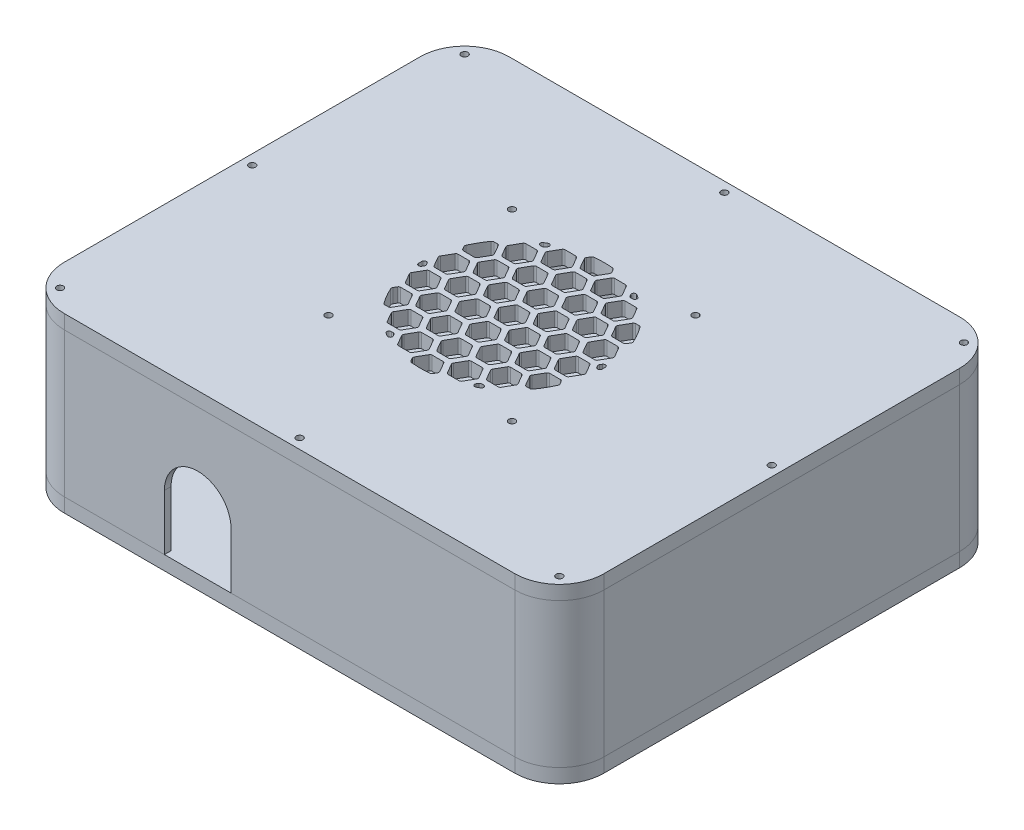
SolidWorks part; units mm, degrees
ref_plane "Front Plane" through (0, 0, 0) normal (0, 0, 1) x (1, 0, 0)
ref_plane "Top Plane" through (0, 0, 0) normal (0, 1, 0) x (1, 0, 0)
ref_plane "Right Plane" through (0, 0, 0) normal (1, 0, 0) x (0, 0, -1)
sketch "Sketch1" plane through (0, 0, 0) normal (0, 1, 0) x (1, 0, 0)
  line L0 (0, 100) -> (242.6, 100) construction
  line L1 (0, 0) -> (242.6, 0)
  line L2 (0, 0) -> (0, 200)
  line L3 (0, 200) -> (242.6, 200)
  line L4 (242.6, 0) -> (242.6, 200)
  line L6 (89, 170) -> (165.6, 170) construction
  line L7 (89, 170) -> (89, 15) construction
  line L8 (89, 15) -> (165.6, 15) construction
  line L9 (165.6, 170) -> (165.6, 15) construction
  line L10 (15, 106) -> (84, 106) construction
  line L11 (15, 106) -> (15, 15) construction
  line L12 (15, 15) -> (84, 15) construction
  line L13 (84, 106) -> (84, 15) construction
  line L14 (170.6, 127) -> (230.6, 127) construction
  line L15 (170.6, 127) -> (170.6, 15) construction
  line L16 (170.6, 15) -> (230.6, 15) construction
  line L17 (230.6, 127) -> (230.6, 15) construction
  line L22 (15, 170) -> (84, 170) construction
  line L23 (15, 170) -> (15, 121) construction
  line L24 (15, 121) -> (84, 121) construction
  line L25 (84, 170) -> (84, 121) construction
  dimension "D1" = 76.6
  dimension "D2" = 155
  dimension "D3" = 69
  dimension "D4" = 91
  dimension "D5" = 60
  dimension "D6" = 112
  dimension "D7" = 15
  dimension "D8" = 5
  dimension "D9" = 5
  dimension "D10" = 12
  dimension "D11" = 30
  dimension "D12" = 15
  dimension "D13" = 15
extrude "Boss-Extrude1" add sketch "Sketch1" along normal blind 6.35
fillet "Fillet1" radius 20 4 edges at (0, 3.175, -200) (242.6, 3.175, -200) (242.6, 3.175, 0) (0, 3.175, 0)
sketch "Sketch2" plane through (0, 6.35, 0) normal (0, 1, 0) x (1, 0, 0)
  line L0 (89, 170) -> (165.6, 170) construction
  line L1 (92.6, 167) -> (162, 167) construction
  line L2 (92.6, 167) -> (92.6, 25) construction
  line L3 (92.6, 25) -> (162, 25) construction
  line L4 (162, 167) -> (162, 25) construction
  line L5 (170.6, 127) -> (230.6, 127) construction
  line L6 (175.6, 65) -> (225.6, 65) construction
  line L7 (175.6, 65) -> (175.6, 40) construction
  line L8 (175.6, 40) -> (225.6, 40) construction
  line L9 (225.6, 65) -> (225.6, 40) construction
  line L11 (15, 170) -> (15, 121) construction
  line L12 (80.996, 125.18) -> (18.004, 125.18) construction
  line L13 (80.996, 125.18) -> (80.996, 165.82) construction
  line L14 (80.996, 165.82) -> (18.004, 165.82) construction
  line L15 (18.004, 125.18) -> (18.004, 165.82) construction
  line L16 (80.996, 125.18) -> (18.004, 165.82) construction
  line L17 (80.996, 165.82) -> (18.004, 125.18) construction
  line L18 (15, 170) -> (84, 170) construction
  line L19 (20, 0) -> (222.6, 0) construction
  circle A0 centre (92.6, 167) radius 1.5
  circle A1 centre (92.6, 25) radius 1.5
  circle A2 centre (162, 25) radius 1.5
  circle A3 centre (162, 167) radius 1.5
  circle A4 centre (175.6, 65) radius 1.5
  circle A5 centre (175.6, 40) radius 1.5
  circle A6 centre (225.6, 65) radius 1.5
  circle A7 centre (225.6, 40) radius 1.5
  circle A8 centre (18.004, 165.82) radius 1.5
  circle A9 centre (80.996, 165.82) radius 1.5
  circle A10 centre (80.996, 125.18) radius 1.5
  circle A11 centre (18.004, 125.18) radius 1.5
  point P6 (127.3, 167)
  point P7 (127.3, 170)
  point P20 (200.6, 65)
  point P23 (200.6, 127)
  point P26 (49.5, 145.5)
  point P34 (15, 145.5)
  point P37 (49.5, 170)
  dimension "D6" = 3
  dimension "D1" = 69.4
  dimension "D2" = 142
  dimension "D3" = 3
  dimension "D4" = 50
  dimension "D5" = 25
  dimension "D7" = 40
  dimension "D8" = 62.992
  dimension "D9" = 40.64
extrude "Cut-Extrude1" cut sketch "Sketch2" against normal through all
sketch "Sketch3" plane through (0, 6.35, 0) normal (0, 1, 0) x (1, 0, 0)
  line L21 (20, 20) -> (9.0398, 9.0398) construction
  line L22 (0, 180) -> (0, 20) construction
  line L23 (6.9185, 11.1612) -> (6.0465, 10.2892)
  line L24 (11.1612, 6.9185) -> (10.2892, 6.0465)
  line L25 (0, 100) -> (242.6, 100) construction
  line L26 (121.3, 200) -> (121.3, 0) construction
  line L27 (231.4388, 6.9185) -> (232.3108, 6.0465)
  line L28 (235.6815, 11.1612) -> (236.5535, 10.2892)
  line L29 (235.6815, 188.8388) -> (236.5535, 189.7108)
  line L30 (231.4388, 193.0815) -> (232.3108, 193.9535)
  line L31 (11.1612, 193.0815) -> (10.2892, 193.9535)
  line L32 (6.9185, 188.8388) -> (6.0465, 189.7108)
  line L33 (242.6, 20) -> (242.6, 180) construction
  line L34 (20, 0) -> (222.6, 0) construction
  line L35 (222.6, 200) -> (20, 200) construction
  line L36 (20, 20) -> (20, 12.5101) construction
  line L37 (3, 180) -> (3, 20)
  line L38 (20, 3) -> (222.6, 3)
  line L39 (239.6, 20) -> (239.6, 180)
  line L40 (222.6, 197) -> (20, 197)
  line L41 (222.6, 200) -> (20, 200)
  line L42 (0, 180) -> (0, 20)
  line L43 (20, 0) -> (222.6, 0)
  line L44 (242.6, 20) -> (242.6, 180)
  line L45 (222.6, 200) -> (20, 200)
  line L46 (0, 180) -> (0, 20)
  line L47 (20, 0) -> (222.6, 0)
  line L48 (242.6, 20) -> (242.6, 180)
  line L49 (4.5, 103) -> (3, 103)
  line L50 (3, 103) -> (3, 97)
  line L51 (3, 97) -> (4.5, 97)
  line L52 (239.6, 103) -> (239.6, 97)
  line L53 (238.1, 103) -> (239.6, 103)
  line L54 (239.6, 97) -> (238.1, 97)
  line L55 (118.3, 195.5) -> (118.3, 197)
  line L56 (124.3, 195.5) -> (124.3, 197)
  line L57 (118.3, 197) -> (124.3, 197)
  line L58 (118.3, 4.5) -> (118.3, 3)
  line L59 (124.3, 4.5) -> (124.3, 3)
  line L60 (118.3, 3) -> (124.3, 3)
  arc A22 (10.2892, 193.9535) -> (6.0465, 189.7108) centre (20, 180) ccw
  arc A24 (6.0465, 10.2892) -> (10.2892, 6.0465) centre (20, 20) ccw
  arc A26 (232.3108, 6.0465) -> (236.5535, 10.2892) centre (222.6, 20) ccw
  arc A28 (236.5535, 189.7108) -> (232.3108, 193.9535) centre (222.6, 180) ccw
  arc A43 (11.1612, 6.9185) -> (6.9185, 11.1612) centre (9.0398, 9.0398) ccw
  circle A44 centre (9.0398, 9.0398) radius 1.5
  circle A45 centre (233.5602, 9.0398) radius 1.5
  arc A46 (231.4388, 6.9185) -> (235.6815, 11.1612) centre (233.5602, 9.0398) cw
  circle A47 centre (233.5602, 190.9602) radius 1.5
  arc A48 (231.4388, 193.0815) -> (235.6815, 188.8388) centre (233.5602, 190.9602) ccw
  circle A49 centre (9.0398, 190.9602) radius 1.5
  arc A50 (11.1612, 193.0815) -> (6.9185, 188.8388) centre (9.0398, 190.9602) cw
  arc A51 (222.6, 0) -> (242.6, 20) centre (222.6, 20) ccw construction
  arc A52 (0, 20) -> (20, 0) centre (20, 20) ccw construction
  arc A53 (242.6, 180) -> (222.6, 200) centre (222.6, 180) ccw construction
  arc A54 (20, 200) -> (0, 180) centre (20, 180) ccw construction
  arc A55 (3, 20) -> (20, 3) centre (20, 20) ccw
  arc A56 (222.6, 3) -> (239.6, 20) centre (222.6, 20) ccw
  arc A57 (239.6, 180) -> (222.6, 197) centre (222.6, 180) ccw
  arc A58 (20, 197) -> (3, 180) centre (20, 180) ccw
  arc A59 (20, 200) -> (0, 180) centre (20, 180) ccw
  arc A60 (0, 20) -> (20, 0) centre (20, 20) ccw
  arc A61 (222.6, 0) -> (242.6, 20) centre (222.6, 20) ccw
  arc A62 (242.6, 180) -> (222.6, 200) centre (222.6, 180) ccw
  arc A63 (20, 200) -> (0, 180) centre (20, 180) ccw
  arc A64 (0, 20) -> (20, 0) centre (20, 20) ccw
  arc A65 (222.6, 0) -> (242.6, 20) centre (222.6, 20) ccw
  arc A66 (242.6, 180) -> (222.6, 200) centre (222.6, 180) ccw
  arc A67 (4.5, 97) -> (4.5, 103) centre (4.5, 100) ccw
  circle A68 centre (4.5, 100) radius 1.5
  arc A69 (238.1, 97) -> (238.1, 103) centre (238.1, 100) cw
  circle A70 centre (238.1, 100) radius 1.5
  circle A71 centre (121.3, 195.5) radius 1.5
  arc A72 (118.3, 195.5) -> (124.3, 195.5) centre (121.3, 195.5) ccw
  circle A73 centre (121.3, 4.5) radius 1.5
  arc A74 (118.3, 4.5) -> (124.3, 4.5) centre (121.3, 4.5) cw
  line M50 (222.6, 200) -> (20, 200)
  arc M51 (20, 200) -> (0, 180) centre (20, 180) ccw
  line M52 (0, 180) -> (0, 20)
  arc M53 (0, 20) -> (20, 0) centre (20, 20) ccw
  line M54 (20, 0) -> (222.6, 0)
  arc M55 (222.6, 0) -> (242.6, 20) centre (222.6, 20) ccw
  line M56 (242.6, 20) -> (242.6, 180)
  arc M57 (242.6, 180) -> (222.6, 200) centre (222.6, 180) ccw
  dimension "D3" = 0
  dimension "D4" = 6
  dimension "D5" = 3
  dimension "D1" = 3
  dimension "D7" = 3
  dimension "D6" = 3
  dimension "D2" = 45
extrude "Boss-Extrude2" add sketch "Sketch3" along normal blind 65 separate body contours M57 M50 M51 M52 M53 M54 M55 M56 | A50 L31 A22 A49 L32 | L37 A68 L50 L51 A67 L49 | A24 A44 L24 A43 L23 | A46 L27 A26 A45 L28 | A74 L58 L38 A73 L60 L59 | L39 A70 L52 L53 A69 L54 | L30 A48 L29 A28 A47 | L55 A72 L56 L40 A71 L57 region at (11.1012, 6.35, -11.1012) region at (3.075, 6.35, -98.5) region at (118.375, 6.35, -3.75) region at (7.0266, 6.35, -190.8543) region at (231.9348, 6.35, -6.5425) region at (119.8, 6.35, -196.925) region at (238.85, 6.35, -97.075) region at (233.4543, 6.35, -192.9734) region at (236.5198, 6.35, -193.9198)
fillet "Fillet5" radius 2 16 edges at (10.2892, 38.85, -193.9535) (6.0465, 38.85, -189.7108) (3, 38.85, -103) (3, 38.85, -97) (6.0465, 38.85, -10.2892) (10.2892, 38.85, -6.0465) (118.3, 38.85, -3) (124.3, 38.85, -3) (232.3108, 38.85, -6.0465) (236.5535, 38.85, -10.2892) (239.6, 38.85, -97) (239.6, 38.85, -103) (232.3108, 38.85, -193.9535) (124.3, 38.85, -197) (118.3, 38.85, -197) (236.5535, 38.85, -189.7108)
sketch "Sketch4" plane through (0, 71.35, 0) normal (0, 1, 0) x (1, 0, 0)
  line L4 (0, 180) -> (0, 20)
  line L5 (222.6, 200) -> (20, 200)
  line L6 (242.6, 20) -> (242.6, 180)
  line L7 (20, 0) -> (222.6, 0)
  line L8 (0, 180) -> (0, 20)
  line L9 (222.6, 200) -> (20, 200)
  line L10 (242.6, 20) -> (242.6, 180)
  line L11 (20, 0) -> (222.6, 0)
  arc A4 (20, 200) -> (0, 180) centre (20, 180) ccw
  arc A5 (242.6, 180) -> (222.6, 200) centre (222.6, 180) ccw
  arc A6 (222.6, 0) -> (242.6, 20) centre (222.6, 20) ccw
  arc A7 (0, 20) -> (20, 0) centre (20, 20) ccw
  arc A8 (20, 200) -> (0, 180) centre (20, 180) ccw
  arc A9 (242.6, 180) -> (222.6, 200) centre (222.6, 180) ccw
  arc A10 (222.6, 0) -> (242.6, 20) centre (222.6, 20) ccw
  arc A11 (0, 20) -> (20, 0) centre (20, 20) ccw
  dimension "D1" = 0
extrude "Boss-Extrude4" add sketch "Sketch4" along normal blind 6.35 separate body
sketch "Sketch5" plane through (0, 77.7, 0) normal (0, 1, 0) x (1, 0, 0)
  line L1 (80.05, 141.25) -> (162.55, 141.25) construction
  line L2 (80.05, 141.25) -> (80.05, 58.75) construction
  line L3 (80.05, 58.75) -> (162.55, 58.75) construction
  line L4 (162.55, 141.25) -> (162.55, 58.75) construction
  line L5 (80.05, 141.25) -> (162.55, 58.75) construction
  line L6 (80.05, 58.75) -> (162.55, 141.25) construction
  line L8 (222.6, 200) -> (20, 200) construction
  line L9 (0, 180) -> (0, 20) construction
  circle A0 centre (80.05, 141.25) radius 1.5
  circle A1 centre (80.05, 58.75) radius 1.5
  circle A2 centre (162.55, 58.75) radius 1.5
  circle A3 centre (162.55, 141.25) radius 1.5
  point P0 (121.3, 100)
  point P11 (121.3, 200)
  point P12 (0, 100)
  dimension "D2" = 3
  dimension "D1" = 82.5
extrude "Cut-Extrude2" cut sketch "Sketch5" against normal through all
sketch "Sketch6" plane through (0, 77.7, 0) normal (0, 1, 0) x (1, 0, 0)
  circle A20 centre (121.3, 4.5) radius 1.5 construction
  circle A21 centre (233.5602, 9.0398) radius 1.5 construction
  circle A22 centre (238.1, 100) radius 1.5 construction
  circle A23 centre (233.5602, 190.9602) radius 1.5 construction
  circle A24 centre (121.3, 195.5) radius 1.5 construction
  circle A25 centre (9.0398, 190.9602) radius 1.5 construction
  circle A26 centre (4.5, 100) radius 1.5 construction
  circle A27 centre (9.0398, 9.0398) radius 1.5 construction
  circle A28 centre (121.3, 4.5) radius 1.5
  circle A29 centre (233.5602, 9.0398) radius 1.5
  circle A30 centre (238.1, 100) radius 1.5
  circle A31 centre (233.5602, 190.9602) radius 1.5
  circle A32 centre (121.3, 195.5) radius 1.5
  circle A33 centre (9.0398, 190.9602) radius 1.5
  circle A34 centre (4.5, 100) radius 1.5
  circle A35 centre (9.0398, 9.0398) radius 1.5
extrude "Cut-Extrude3" cut sketch "Sketch6" against normal through all
sketch "Sketch7" plane through (0, 77.7, 0) normal (0, 1, 0) x (1, 0, 0)
  line L0 (80.05, 141.25) -> (162.55, 141.25) construction
  line L1 (80.05, 141.25) -> (80.05, 58.75) construction
  line L2 (80.05, 58.75) -> (162.55, 58.75) construction
  line L3 (162.55, 141.25) -> (162.55, 58.75) construction
  line L4 (80.05, 141.25) -> (162.55, 141.25) construction
  line L5 (80.05, 141.25) -> (80.05, 58.75) construction
  line L6 (80.05, 58.75) -> (162.55, 58.75) construction
  line L7 (162.55, 141.25) -> (162.55, 58.75) construction
  line L8 (157.7952, 124.5346) -> (151.7952, 124.5346)
  line L9 (124.3, 105.1962) -> (118.3, 105.1962)
  line L10 (118.3, 105.1962) -> (115.3, 100)
  line L11 (115.3, 100) -> (118.3, 94.8038)
  line L12 (118.3, 94.8038) -> (124.3, 94.8038)
  line L13 (124.3, 94.8038) -> (127.3, 100)
  line L14 (127.3, 100) -> (124.3, 105.1962)
  line L15 (138.4651, 106.4462) -> (135.4651, 111.6423)
  line L16 (135.4651, 111.6423) -> (129.4651, 111.6423)
  line L17 (129.4651, 111.6423) -> (126.4651, 106.4462)
  line L18 (126.4651, 106.4462) -> (129.4651, 101.25)
  line L19 (129.4651, 101.25) -> (135.4651, 101.25)
  line L20 (135.4651, 101.25) -> (138.4651, 106.4462)
  line L21 (127.3, 112.8923) -> (124.3, 118.0885)
  line L22 (124.3, 118.0885) -> (118.3, 118.0885)
  line L23 (118.3, 118.0885) -> (115.3, 112.8923)
  line L24 (115.3, 112.8923) -> (118.3, 107.6962)
  line L25 (118.3, 107.6962) -> (124.3, 107.6962)
  line L26 (124.3, 107.6962) -> (127.3, 112.8923)
  line L27 (135.4651, 124.5346) -> (129.4651, 124.5346)
  line L28 (129.4651, 124.5346) -> (126.4651, 119.3385)
  line L29 (126.4651, 119.3385) -> (129.4651, 114.1423)
  line L30 (129.4651, 114.1423) -> (135.4651, 114.1423)
  line L31 (135.4651, 114.1423) -> (138.4651, 119.3385)
  line L32 (138.4651, 119.3385) -> (135.4651, 124.5346)
  line L33 (151.7952, 124.5346) -> (148.7952, 119.3385)
  line L34 (148.7952, 119.3385) -> (151.7952, 114.1423)
  line L35 (151.7952, 114.1423) -> (157.7952, 114.1423)
  line L36 (157.7952, 114.1423) -> (160.7952, 119.3385)
  line L37 (160.7952, 119.3385) -> (157.7952, 124.5346)
  line L38 (149.6301, 112.8923) -> (146.6301, 118.0885)
  line L39 (146.6301, 118.0885) -> (140.6301, 118.0885)
  line L40 (140.6301, 118.0885) -> (137.6301, 112.8923)
  line L41 (137.6301, 112.8923) -> (140.6301, 107.6962)
  line L42 (140.6301, 107.6962) -> (146.6301, 107.6962)
  line L43 (146.6301, 107.6962) -> (149.6301, 112.8923)
  line L44 (146.6301, 105.1962) -> (140.6301, 105.1962)
  line L45 (140.6301, 105.1962) -> (137.6301, 100)
  line L46 (137.6301, 100) -> (140.6301, 94.8038)
  line L47 (140.6301, 94.8038) -> (146.6301, 94.8038)
  line L48 (146.6301, 94.8038) -> (149.6301, 100)
  line L49 (149.6301, 100) -> (146.6301, 105.1962)
  line L50 (160.7952, 106.4462) -> (157.7952, 111.6423)
  line L51 (157.7952, 111.6423) -> (151.7952, 111.6423)
  line L52 (151.7952, 111.6423) -> (148.7952, 106.4462)
  line L53 (148.7952, 106.4462) -> (151.7952, 101.25)
  line L54 (151.7952, 101.25) -> (157.7952, 101.25)
  line L55 (157.7952, 101.25) -> (160.7952, 106.4462)
  line L56 (180.1253, 124.5346) -> (174.1253, 124.5346)
  line L57 (174.1253, 124.5346) -> (171.1253, 119.3385)
  line L58 (171.1253, 119.3385) -> (174.1253, 114.1423)
  line L59 (174.1253, 114.1423) -> (180.1253, 114.1423)
  line L60 (180.1253, 114.1423) -> (183.1253, 119.3385)
  line L61 (183.1253, 119.3385) -> (180.1253, 124.5346)
  line L62 (171.9603, 112.8923) -> (168.9603, 118.0885)
  line L63 (168.9603, 118.0885) -> (162.9603, 118.0885)
  line L64 (162.9603, 118.0885) -> (159.9603, 112.8923)
  line L65 (159.9603, 112.8923) -> (162.9603, 107.6962)
  line L66 (162.9603, 107.6962) -> (168.9603, 107.6962)
  line L67 (168.9603, 107.6962) -> (171.9603, 112.8923)
  line L68 (168.9603, 105.1962) -> (162.9603, 105.1962)
  line L69 (162.9603, 105.1962) -> (159.9603, 100)
  line L70 (159.9603, 100) -> (162.9603, 94.8038)
  line L71 (162.9603, 94.8038) -> (168.9603, 94.8038)
  line L72 (168.9603, 94.8038) -> (171.9603, 100)
  line L73 (171.9603, 100) -> (168.9603, 105.1962)
  line L74 (183.1253, 106.4462) -> (180.1253, 111.6423)
  line L75 (180.1253, 111.6423) -> (174.1253, 111.6423)
  line L76 (174.1253, 111.6423) -> (171.1253, 106.4462)
  line L77 (171.1253, 106.4462) -> (174.1253, 101.25)
  line L78 (174.1253, 101.25) -> (180.1253, 101.25)
  line L79 (180.1253, 101.25) -> (183.1253, 106.4462)
  line L80 (157.7952, 150.3192) -> (151.7952, 150.3192)
  line L81 (151.7952, 150.3192) -> (148.7952, 145.1231)
  line L82 (148.7952, 145.1231) -> (151.7952, 139.9269)
  line L83 (151.7952, 139.9269) -> (157.7952, 139.9269)
  line L84 (157.7952, 139.9269) -> (160.7952, 145.1231)
  line L85 (160.7952, 145.1231) -> (157.7952, 150.3192)
  line L86 (149.6301, 138.6769) -> (146.6301, 143.8731)
  line L87 (146.6301, 143.8731) -> (140.6301, 143.8731)
  line L88 (140.6301, 143.8731) -> (137.6301, 138.6769)
  line L89 (137.6301, 138.6769) -> (140.6301, 133.4808)
  line L90 (140.6301, 133.4808) -> (146.6301, 133.4808)
  line L91 (146.6301, 133.4808) -> (149.6301, 138.6769)
  line L92 (146.6301, 130.9808) -> (140.6301, 130.9808)
  line L93 (140.6301, 130.9808) -> (137.6301, 125.7846)
  line L94 (137.6301, 125.7846) -> (140.6301, 120.5885)
  line L95 (140.6301, 120.5885) -> (146.6301, 120.5885)
  line L96 (146.6301, 120.5885) -> (149.6301, 125.7846)
  line L97 (149.6301, 125.7846) -> (146.6301, 130.9808)
  line L98 (160.7952, 132.2308) -> (157.7952, 137.4269)
  line L99 (157.7952, 137.4269) -> (151.7952, 137.4269)
  line L100 (151.7952, 137.4269) -> (148.7952, 132.2308)
  line L101 (148.7952, 132.2308) -> (151.7952, 127.0346)
  line L102 (151.7952, 127.0346) -> (157.7952, 127.0346)
  line L103 (157.7952, 127.0346) -> (160.7952, 132.2308)
  line L104 (180.1253, 150.3192) -> (174.1253, 150.3192)
  line L105 (174.1253, 150.3192) -> (171.1253, 145.1231)
  line L106 (171.1253, 145.1231) -> (174.1253, 139.9269)
  line L107 (174.1253, 139.9269) -> (180.1253, 139.9269)
  line L108 (180.1253, 139.9269) -> (183.1253, 145.1231)
  line L109 (183.1253, 145.1231) -> (180.1253, 150.3192)
  line L110 (171.9603, 138.6769) -> (168.9603, 143.8731)
  line L111 (168.9603, 143.8731) -> (162.9603, 143.8731)
  line L112 (162.9603, 143.8731) -> (159.9603, 138.6769)
  line L113 (159.9603, 138.6769) -> (162.9603, 133.4808)
  line L114 (162.9603, 133.4808) -> (168.9603, 133.4808)
  line L115 (168.9603, 133.4808) -> (171.9603, 138.6769)
  line L116 (168.9603, 130.9808) -> (162.9603, 130.9808)
  line L117 (162.9603, 130.9808) -> (159.9603, 125.7846)
  line L118 (159.9603, 125.7846) -> (162.9603, 120.5885)
  line L119 (162.9603, 120.5885) -> (168.9603, 120.5885)
  line L120 (168.9603, 120.5885) -> (171.9603, 125.7846)
  line L121 (171.9603, 125.7846) -> (168.9603, 130.9808)
  line L122 (183.1253, 132.2308) -> (180.1253, 137.4269)
  line L123 (180.1253, 137.4269) -> (174.1253, 137.4269)
  line L124 (174.1253, 137.4269) -> (171.1253, 132.2308)
  line L125 (171.1253, 132.2308) -> (174.1253, 127.0346)
  line L126 (174.1253, 127.0346) -> (180.1253, 127.0346)
  line L127 (180.1253, 127.0346) -> (183.1253, 132.2308)
  line L128 (135.4651, 150.3192) -> (129.4651, 150.3192)
  line L129 (129.4651, 150.3192) -> (126.4651, 145.1231)
  line L130 (126.4651, 145.1231) -> (129.4651, 139.9269)
  line L131 (129.4651, 139.9269) -> (135.4651, 139.9269)
  line L132 (135.4651, 139.9269) -> (138.4651, 145.1231)
  line L133 (138.4651, 145.1231) -> (135.4651, 150.3192)
  line L134 (127.3, 138.6769) -> (124.3, 143.8731)
  line L135 (124.3, 143.8731) -> (118.3, 143.8731)
  line L136 (118.3, 143.8731) -> (115.3, 138.6769)
  line L137 (115.3, 138.6769) -> (118.3, 133.4808)
  line L138 (118.3, 133.4808) -> (124.3, 133.4808)
  line L139 (124.3, 133.4808) -> (127.3, 138.6769)
  line L140 (124.3, 130.9808) -> (118.3, 130.9808)
  line L141 (118.3, 130.9808) -> (115.3, 125.7846)
  line L142 (115.3, 125.7846) -> (118.3, 120.5885)
  line L143 (118.3, 120.5885) -> (124.3, 120.5885)
  line L144 (124.3, 120.5885) -> (127.3, 125.7846)
  line L145 (127.3, 125.7846) -> (124.3, 130.9808)
  line L146 (138.4651, 132.2308) -> (135.4651, 137.4269)
  line L147 (135.4651, 137.4269) -> (129.4651, 137.4269)
  line L148 (129.4651, 137.4269) -> (126.4651, 132.2308)
  line L149 (126.4651, 132.2308) -> (129.4651, 127.0346)
  line L150 (129.4651, 127.0346) -> (135.4651, 127.0346)
  line L151 (135.4651, 127.0346) -> (138.4651, 132.2308)
  line L152 (124.3, 92.3038) -> (118.3, 92.3038)
  line L153 (118.3, 92.3038) -> (115.3, 87.1077)
  line L154 (115.3, 87.1077) -> (118.3, 81.9115)
  line L155 (118.3, 81.9115) -> (124.3, 81.9115)
  line L156 (124.3, 81.9115) -> (127.3, 87.1077)
  line L157 (127.3, 87.1077) -> (124.3, 92.3038)
  line L158 (138.4651, 93.5538) -> (135.4651, 98.75)
  line L159 (135.4651, 98.75) -> (129.4651, 98.75)
  line L160 (129.4651, 98.75) -> (126.4651, 93.5538)
  line L161 (126.4651, 93.5538) -> (129.4651, 88.3577)
  line L162 (129.4651, 88.3577) -> (135.4651, 88.3577)
  line L163 (135.4651, 88.3577) -> (138.4651, 93.5538)
  line L164 (160.7952, 93.5538) -> (157.7952, 98.75)
  line L165 (157.7952, 98.75) -> (151.7952, 98.75)
  line L166 (151.7952, 98.75) -> (148.7952, 93.5538)
  line L167 (148.7952, 93.5538) -> (151.7952, 88.3577)
  line L168 (151.7952, 88.3577) -> (157.7952, 88.3577)
  line L169 (157.7952, 88.3577) -> (160.7952, 93.5538)
  line L170 (168.9603, 92.3038) -> (162.9603, 92.3038)
  line L171 (162.9603, 92.3038) -> (159.9603, 87.1077)
  line L172 (159.9603, 87.1077) -> (162.9603, 81.9115)
  line L173 (162.9603, 81.9115) -> (168.9603, 81.9115)
  line L174 (168.9603, 81.9115) -> (171.9603, 87.1077)
  line L175 (171.9603, 87.1077) -> (168.9603, 92.3038)
  line L176 (146.6301, 92.3038) -> (140.6301, 92.3038)
  line L177 (140.6301, 92.3038) -> (137.6301, 87.1077)
  line L178 (137.6301, 87.1077) -> (140.6301, 81.9115)
  line L179 (140.6301, 81.9115) -> (146.6301, 81.9115)
  line L180 (146.6301, 81.9115) -> (149.6301, 87.1077)
  line L181 (149.6301, 87.1077) -> (146.6301, 92.3038)
  line L182 (124.3, 79.4115) -> (118.3, 79.4115)
  line L183 (118.3, 79.4115) -> (115.3, 74.2154)
  line L184 (115.3, 74.2154) -> (118.3, 69.0192)
  line L185 (118.3, 69.0192) -> (124.3, 69.0192)
  line L186 (124.3, 69.0192) -> (127.3, 74.2154)
  line L187 (127.3, 74.2154) -> (124.3, 79.4115)
  line L188 (138.4651, 80.6615) -> (135.4651, 85.8577)
  line L189 (135.4651, 85.8577) -> (129.4651, 85.8577)
  line L190 (129.4651, 85.8577) -> (126.4651, 80.6615)
  line L191 (126.4651, 80.6615) -> (129.4651, 75.4654)
  line L192 (129.4651, 75.4654) -> (135.4651, 75.4654)
  line L193 (135.4651, 75.4654) -> (138.4651, 80.6615)
  line L194 (160.7952, 80.6615) -> (157.7952, 85.8577)
  line L195 (157.7952, 85.8577) -> (151.7952, 85.8577)
  line L196 (151.7952, 85.8577) -> (148.7952, 80.6615)
  line L197 (148.7952, 80.6615) -> (151.7952, 75.4654)
  line L198 (151.7952, 75.4654) -> (157.7952, 75.4654)
  line L199 (157.7952, 75.4654) -> (160.7952, 80.6615)
  line L200 (168.9603, 79.4115) -> (162.9603, 79.4115)
  line L201 (162.9603, 79.4115) -> (159.9603, 74.2154)
  line L202 (159.9603, 74.2154) -> (162.9603, 69.0192)
  line L203 (162.9603, 69.0192) -> (168.9603, 69.0192)
  line L204 (168.9603, 69.0192) -> (171.9603, 74.2154)
  line L205 (171.9603, 74.2154) -> (168.9603, 79.4115)
  line L206 (146.6301, 79.4115) -> (140.6301, 79.4115)
  line L207 (140.6301, 79.4115) -> (137.6301, 74.2154)
  line L208 (137.6301, 74.2154) -> (140.6301, 69.0192)
  line L209 (140.6301, 69.0192) -> (146.6301, 69.0192)
  line L210 (146.6301, 69.0192) -> (149.6301, 74.2154)
  line L211 (149.6301, 74.2154) -> (146.6301, 79.4115)
  line L212 (124.3, 66.5192) -> (118.3, 66.5192)
  line L213 (118.3, 66.5192) -> (115.3, 61.3231)
  line L214 (115.3, 61.3231) -> (118.3, 56.1269)
  line L215 (118.3, 56.1269) -> (124.3, 56.1269)
  line L216 (124.3, 56.1269) -> (127.3, 61.3231)
  line L217 (127.3, 61.3231) -> (124.3, 66.5192)
  line L218 (138.4651, 67.7692) -> (135.4651, 72.9654)
  line L219 (135.4651, 72.9654) -> (129.4651, 72.9654)
  line L220 (129.4651, 72.9654) -> (126.4651, 67.7692)
  line L221 (126.4651, 67.7692) -> (129.4651, 62.5731)
  line L222 (129.4651, 62.5731) -> (135.4651, 62.5731)
  line L223 (135.4651, 62.5731) -> (138.4651, 67.7692)
  line L224 (160.7952, 67.7692) -> (157.7952, 72.9654)
  line L225 (157.7952, 72.9654) -> (151.7952, 72.9654)
  line L226 (151.7952, 72.9654) -> (148.7952, 67.7692)
  line L227 (148.7952, 67.7692) -> (151.7952, 62.5731)
  line L228 (151.7952, 62.5731) -> (157.7952, 62.5731)
  line L229 (157.7952, 62.5731) -> (160.7952, 67.7692)
  line L230 (168.9603, 66.5192) -> (162.9603, 66.5192)
  line L231 (162.9603, 66.5192) -> (159.9603, 61.3231)
  line L232 (159.9603, 61.3231) -> (162.9603, 56.1269)
  line L233 (162.9603, 56.1269) -> (168.9603, 56.1269)
  line L234 (168.9603, 56.1269) -> (171.9603, 61.3231)
  line L235 (171.9603, 61.3231) -> (168.9603, 66.5192)
  line L236 (146.6301, 66.5192) -> (140.6301, 66.5192)
  line L237 (140.6301, 66.5192) -> (137.6301, 61.3231)
  line L238 (137.6301, 61.3231) -> (140.6301, 56.1269)
  line L239 (140.6301, 56.1269) -> (146.6301, 56.1269)
  line L240 (146.6301, 56.1269) -> (149.6301, 61.3231)
  line L241 (149.6301, 61.3231) -> (146.6301, 66.5192)
  line L242 (124.3, 53.6269) -> (118.3, 53.6269)
  line L243 (118.3, 53.6269) -> (115.3, 48.4308)
  line L244 (115.3, 48.4308) -> (118.3, 43.2346)
  line L245 (118.3, 43.2346) -> (124.3, 43.2346)
  line L246 (124.3, 43.2346) -> (127.3, 48.4308)
  line L247 (127.3, 48.4308) -> (124.3, 53.6269)
  line L248 (138.4651, 54.8769) -> (135.4651, 60.0731)
  line L249 (135.4651, 60.0731) -> (129.4651, 60.0731)
  line L250 (129.4651, 60.0731) -> (126.4651, 54.8769)
  line L251 (126.4651, 54.8769) -> (129.4651, 49.6808)
  line L252 (129.4651, 49.6808) -> (135.4651, 49.6808)
  line L253 (135.4651, 49.6808) -> (138.4651, 54.8769)
  line L254 (160.7952, 54.8769) -> (157.7952, 60.0731)
  line L255 (157.7952, 60.0731) -> (151.7952, 60.0731)
  line L256 (151.7952, 60.0731) -> (148.7952, 54.8769)
  line L257 (148.7952, 54.8769) -> (151.7952, 49.6808)
  line L258 (151.7952, 49.6808) -> (157.7952, 49.6808)
  line L259 (157.7952, 49.6808) -> (160.7952, 54.8769)
  line L260 (168.9603, 53.6269) -> (162.9603, 53.6269)
  line L261 (162.9603, 53.6269) -> (159.9603, 48.4308)
  line L262 (159.9603, 48.4308) -> (162.9603, 43.2346)
  line L263 (162.9603, 43.2346) -> (168.9603, 43.2346)
  line L264 (168.9603, 43.2346) -> (171.9603, 48.4308)
  line L265 (171.9603, 48.4308) -> (168.9603, 53.6269)
  line L266 (146.6301, 53.6269) -> (140.6301, 53.6269)
  line L267 (140.6301, 53.6269) -> (137.6301, 48.4308)
  line L268 (137.6301, 48.4308) -> (140.6301, 43.2346)
  line L269 (140.6301, 43.2346) -> (146.6301, 43.2346)
  line L270 (146.6301, 43.2346) -> (149.6301, 48.4308)
  line L271 (149.6301, 48.4308) -> (146.6301, 53.6269)
  line L272 (104.9699, 138.6769) -> (101.9699, 143.8731)
  line L273 (101.9699, 143.8731) -> (95.9699, 143.8731)
  line L274 (95.9699, 143.8731) -> (92.9699, 138.6769)
  line L275 (92.9699, 138.6769) -> (95.9699, 133.4808)
  line L276 (95.9699, 133.4808) -> (101.9699, 133.4808)
  line L277 (101.9699, 133.4808) -> (104.9699, 138.6769)
  line L278 (101.9699, 130.9808) -> (95.9699, 130.9808)
  line L279 (95.9699, 130.9808) -> (92.9699, 125.7846)
  line L280 (92.9699, 125.7846) -> (95.9699, 120.5885)
  line L281 (95.9699, 120.5885) -> (101.9699, 120.5885)
  line L282 (101.9699, 120.5885) -> (104.9699, 125.7846)
  line L283 (104.9699, 125.7846) -> (101.9699, 130.9808)
  line L284 (101.9699, 92.3038) -> (95.9699, 92.3038)
  line L285 (95.9699, 92.3038) -> (92.9699, 87.1077)
  line L286 (92.9699, 87.1077) -> (95.9699, 81.9115)
  line L287 (95.9699, 81.9115) -> (101.9699, 81.9115)
  line L288 (101.9699, 81.9115) -> (104.9699, 87.1077)
  line L289 (104.9699, 87.1077) -> (101.9699, 92.3038)
  line L290 (101.9699, 79.4115) -> (95.9699, 79.4115)
  line L291 (95.9699, 79.4115) -> (92.9699, 74.2154)
  line L292 (92.9699, 74.2154) -> (95.9699, 69.0192)
  line L293 (95.9699, 69.0192) -> (101.9699, 69.0192)
  line L294 (101.9699, 69.0192) -> (104.9699, 74.2154)
  line L295 (104.9699, 74.2154) -> (101.9699, 79.4115)
  line L296 (101.9699, 66.5192) -> (95.9699, 66.5192)
  line L297 (95.9699, 66.5192) -> (92.9699, 61.3231)
  line L298 (92.9699, 61.3231) -> (95.9699, 56.1269)
  line L299 (95.9699, 56.1269) -> (101.9699, 56.1269)
  line L300 (101.9699, 56.1269) -> (104.9699, 61.3231)
  line L301 (104.9699, 61.3231) -> (101.9699, 66.5192)
  line L302 (116.1349, 67.7692) -> (113.1349, 72.9654)
  line L303 (113.1349, 72.9654) -> (107.1349, 72.9654)
  line L304 (107.1349, 72.9654) -> (104.1349, 67.7692)
  line L305 (104.1349, 67.7692) -> (107.1349, 62.5731)
  line L306 (107.1349, 62.5731) -> (113.1349, 62.5731)
  line L307 (113.1349, 62.5731) -> (116.1349, 67.7692)
  line L308 (116.1349, 80.6615) -> (113.1349, 85.8577)
  line L309 (113.1349, 85.8577) -> (107.1349, 85.8577)
  line L310 (107.1349, 85.8577) -> (104.1349, 80.6615)
  line L311 (104.1349, 80.6615) -> (107.1349, 75.4654)
  line L312 (107.1349, 75.4654) -> (113.1349, 75.4654)
  line L313 (113.1349, 75.4654) -> (116.1349, 80.6615)
  line L314 (101.9699, 105.1962) -> (95.9699, 105.1962)
  line L315 (95.9699, 105.1962) -> (92.9699, 100)
  line L316 (92.9699, 100) -> (95.9699, 94.8038)
  line L317 (95.9699, 94.8038) -> (101.9699, 94.8038)
  line L318 (101.9699, 94.8038) -> (104.9699, 100)
  line L319 (104.9699, 100) -> (101.9699, 105.1962)
  line L320 (116.1349, 93.5538) -> (113.1349, 98.75)
  line L321 (113.1349, 98.75) -> (107.1349, 98.75)
  line L322 (107.1349, 98.75) -> (104.1349, 93.5538)
  line L323 (104.1349, 93.5538) -> (107.1349, 88.3577)
  line L324 (107.1349, 88.3577) -> (113.1349, 88.3577)
  line L325 (113.1349, 88.3577) -> (116.1349, 93.5538)
  line L326 (116.1349, 106.4462) -> (113.1349, 111.6423)
  line L327 (113.1349, 111.6423) -> (107.1349, 111.6423)
  line L328 (107.1349, 111.6423) -> (104.1349, 106.4462)
  line L329 (104.1349, 106.4462) -> (107.1349, 101.25)
  line L330 (107.1349, 101.25) -> (113.1349, 101.25)
  line L331 (113.1349, 101.25) -> (116.1349, 106.4462)
  line L332 (104.9699, 112.8923) -> (101.9699, 118.0885)
  line L333 (101.9699, 118.0885) -> (95.9699, 118.0885)
  line L334 (95.9699, 118.0885) -> (92.9699, 112.8923)
  line L335 (92.9699, 112.8923) -> (95.9699, 107.6962)
  line L336 (95.9699, 107.6962) -> (101.9699, 107.6962)
  line L337 (101.9699, 107.6962) -> (104.9699, 112.8923)
  line L338 (113.1349, 124.5346) -> (107.1349, 124.5346)
  line L339 (107.1349, 124.5346) -> (104.1349, 119.3385)
  line L340 (104.1349, 119.3385) -> (107.1349, 114.1423)
  line L341 (107.1349, 114.1423) -> (113.1349, 114.1423)
  line L342 (113.1349, 114.1423) -> (116.1349, 119.3385)
  line L343 (116.1349, 119.3385) -> (113.1349, 124.5346)
  line L344 (116.1349, 132.2308) -> (113.1349, 137.4269)
  line L345 (113.1349, 137.4269) -> (107.1349, 137.4269)
  line L346 (107.1349, 137.4269) -> (104.1349, 132.2308)
  line L347 (104.1349, 132.2308) -> (107.1349, 127.0346)
  line L348 (107.1349, 127.0346) -> (113.1349, 127.0346)
  line L349 (113.1349, 127.0346) -> (116.1349, 132.2308)
  line L350 (116.1349, 54.8769) -> (113.1349, 60.0731)
  line L351 (113.1349, 60.0731) -> (107.1349, 60.0731)
  line L352 (107.1349, 60.0731) -> (104.1349, 54.8769)
  line L353 (104.1349, 54.8769) -> (107.1349, 49.6808)
  line L354 (107.1349, 49.6808) -> (113.1349, 49.6808)
  line L355 (113.1349, 49.6808) -> (116.1349, 54.8769)
  line L356 (82.6397, 138.6769) -> (79.6397, 143.8731)
  line L357 (79.6397, 143.8731) -> (73.6397, 143.8731)
  line L358 (73.6397, 143.8731) -> (70.6397, 138.6769)
  line L359 (70.6397, 138.6769) -> (73.6397, 133.4808)
  line L360 (73.6397, 133.4808) -> (79.6397, 133.4808)
  line L361 (79.6397, 133.4808) -> (82.6397, 138.6769)
  line L362 (79.6397, 130.9808) -> (73.6397, 130.9808)
  line L363 (73.6397, 130.9808) -> (70.6397, 125.7846)
  line L364 (70.6397, 125.7846) -> (73.6397, 120.5885)
  line L365 (73.6397, 120.5885) -> (79.6397, 120.5885)
  line L366 (79.6397, 120.5885) -> (82.6397, 125.7846)
  line L367 (82.6397, 125.7846) -> (79.6397, 130.9808)
  line L368 (79.6397, 92.3038) -> (73.6397, 92.3038)
  line L369 (73.6397, 92.3038) -> (70.6397, 87.1077)
  line L370 (70.6397, 87.1077) -> (73.6397, 81.9115)
  line L371 (73.6397, 81.9115) -> (79.6397, 81.9115)
  line L372 (79.6397, 81.9115) -> (82.6397, 87.1077)
  line L373 (82.6397, 87.1077) -> (79.6397, 92.3038)
  line L374 (79.6397, 79.4115) -> (73.6397, 79.4115)
  line L375 (73.6397, 79.4115) -> (70.6397, 74.2154)
  line L376 (70.6397, 74.2154) -> (73.6397, 69.0192)
  line L377 (73.6397, 69.0192) -> (79.6397, 69.0192)
  line L378 (79.6397, 69.0192) -> (82.6397, 74.2154)
  line L379 (82.6397, 74.2154) -> (79.6397, 79.4115)
  line L380 (79.6397, 66.5192) -> (73.6397, 66.5192)
  line L381 (73.6397, 66.5192) -> (70.6397, 61.3231)
  line L382 (70.6397, 61.3231) -> (73.6397, 56.1269)
  line L383 (73.6397, 56.1269) -> (79.6397, 56.1269)
  line L384 (79.6397, 56.1269) -> (82.6397, 61.3231)
  line L385 (82.6397, 61.3231) -> (79.6397, 66.5192)
  line L386 (93.8048, 67.7692) -> (90.8048, 72.9654)
  line L387 (90.8048, 72.9654) -> (84.8048, 72.9654)
  line L388 (84.8048, 72.9654) -> (81.8048, 67.7692)
  line L389 (81.8048, 67.7692) -> (84.8048, 62.5731)
  line L390 (84.8048, 62.5731) -> (90.8048, 62.5731)
  line L391 (90.8048, 62.5731) -> (93.8048, 67.7692)
  line L392 (93.8048, 80.6615) -> (90.8048, 85.8577)
  line L393 (90.8048, 85.8577) -> (84.8048, 85.8577)
  line L394 (84.8048, 85.8577) -> (81.8048, 80.6615)
  line L395 (81.8048, 80.6615) -> (84.8048, 75.4654)
  line L396 (84.8048, 75.4654) -> (90.8048, 75.4654)
  line L397 (90.8048, 75.4654) -> (93.8048, 80.6615)
  line L398 (79.6397, 105.1962) -> (73.6397, 105.1962)
  line L399 (73.6397, 105.1962) -> (70.6397, 100)
  line L400 (70.6397, 100) -> (73.6397, 94.8038)
  line L401 (73.6397, 94.8038) -> (79.6397, 94.8038)
  line L402 (79.6397, 94.8038) -> (82.6397, 100)
  line L403 (82.6397, 100) -> (79.6397, 105.1962)
  line L404 (93.8048, 93.5538) -> (90.8048, 98.75)
  line L405 (90.8048, 98.75) -> (84.8048, 98.75)
  line L406 (84.8048, 98.75) -> (81.8048, 93.5538)
  line L407 (81.8048, 93.5538) -> (84.8048, 88.3577)
  line L408 (84.8048, 88.3577) -> (90.8048, 88.3577)
  line L409 (90.8048, 88.3577) -> (93.8048, 93.5538)
  line L410 (93.8048, 106.4462) -> (90.8048, 111.6423)
  line L411 (90.8048, 111.6423) -> (84.8048, 111.6423)
  line L412 (84.8048, 111.6423) -> (81.8048, 106.4462)
  line L413 (81.8048, 106.4462) -> (84.8048, 101.25)
  line L414 (84.8048, 101.25) -> (90.8048, 101.25)
  line L415 (90.8048, 101.25) -> (93.8048, 106.4462)
  line L416 (82.6397, 112.8923) -> (79.6397, 118.0885)
  line L417 (79.6397, 118.0885) -> (73.6397, 118.0885)
  line L418 (73.6397, 118.0885) -> (70.6397, 112.8923)
  line L419 (70.6397, 112.8923) -> (73.6397, 107.6962)
  line L420 (73.6397, 107.6962) -> (79.6397, 107.6962)
  line L421 (79.6397, 107.6962) -> (82.6397, 112.8923)
  line L422 (90.8048, 124.5346) -> (84.8048, 124.5346)
  line L423 (84.8048, 124.5346) -> (81.8048, 119.3385)
  line L424 (81.8048, 119.3385) -> (84.8048, 114.1423)
  line L425 (84.8048, 114.1423) -> (90.8048, 114.1423)
  line L426 (90.8048, 114.1423) -> (93.8048, 119.3385)
  line L427 (93.8048, 119.3385) -> (90.8048, 124.5346)
  line L428 (93.8048, 132.2308) -> (90.8048, 137.4269)
  line L429 (90.8048, 137.4269) -> (84.8048, 137.4269)
  line L430 (84.8048, 137.4269) -> (81.8048, 132.2308)
  line L431 (81.8048, 132.2308) -> (84.8048, 127.0346)
  line L432 (84.8048, 127.0346) -> (90.8048, 127.0346)
  line L433 (90.8048, 127.0346) -> (93.8048, 132.2308)
  line L434 (93.8048, 54.8769) -> (90.8048, 60.0731)
  line L435 (90.8048, 60.0731) -> (84.8048, 60.0731)
  line L436 (84.8048, 60.0731) -> (81.8048, 54.8769)
  line L437 (81.8048, 54.8769) -> (84.8048, 49.6808)
  line L438 (84.8048, 49.6808) -> (90.8048, 49.6808)
  line L439 (90.8048, 49.6808) -> (93.8048, 54.8769)
  line L440 (116.1349, 145.1231) -> (113.1349, 150.3192)
  line L441 (113.1349, 150.3192) -> (107.1349, 150.3192)
  line L442 (107.1349, 150.3192) -> (104.1349, 145.1231)
  line L443 (104.1349, 145.1231) -> (107.1349, 139.9269)
  line L444 (107.1349, 139.9269) -> (113.1349, 139.9269)
  line L445 (113.1349, 139.9269) -> (116.1349, 145.1231)
  circle A0 centre (121.3, 100) radius 41.25
  circle A4 centre (121.3, 100) radius 5.1962 construction
  circle A5 centre (132.4651, 106.4462) radius 5.1962 construction
  circle A6 centre (121.3, 112.8923) radius 5.1962 construction
  circle A7 centre (132.4651, 119.3385) radius 5.1962 construction
  point P15 (125.8, 115.4904)
  dimension "D1" = 6
  dimension "D2" = 2.5
  dimension "D3" = 1.25
  dimension "D4" = 2.5
  dimension "D5" = 2.5
  dimension "D6" = 2.5
  dimension "D11" = 2.5
  dimension "D12" = 2.5
  dimension "D13" = 2.5
  dimension "D14" = 2.5
  dimension "D15" = 2.5
  dimension "D17" = 2.5
  dimension "D7" = 3
  dimension "D8" = 2
  dimension "D9" = 5
  dimension "D10" = 3
  dimension "D16" = 2
extrude "Cut-Extrude8" cut sketch "Sketch7" against normal blind 12.35 contours A0
extrude "Boss-Extrude5" add sketch "Sketch7<4>" against normal up to surface (6.35 mm away) contours L216 A0 L222 L221 L220 L219 L218 L223 L237 L236 L209 L208 L207 L206 L211 L210 L198 L197 L196 L195 L194 L169 L168 L167 L166 L165 L164 L70 L69 L55 L54 L53 L52 L51 L50 L36 L35 L34 L33 L8 L97 L96 L95 | L387 A0 L386 | L373 A0 L372 | L416 A0 L421 | L433 A0 L432 | L445 A0 L444 | L131 A0 L130 | L102 A0 L101 | L65 A0 L64 | L172 A0 L171 | L226 A0 L225 | L250 A0 L249 | L351 A0 L350 region at (153.1278, 77.7, -125.6947) region at (151.6455, 77.7, -127.6864) region at (160.4498, 77.7, -112.4367) region at (130.1044, 77.7, -140.1231) region at (160.4498, 77.7, -87.5633) region at (112.4956, 77.7, -140.1231) region at (151.6455, 77.7, -72.3136) region at (90.9545, 77.7, -127.6864) region at (130.1044, 77.7, -59.8769) region at (82.1502, 77.7, -112.4367) region at (112.4956, 77.7, -59.8769) region at (82.1502, 77.7, -87.5633) region at (90.9545, 77.7, -72.3136) up to face at (121.3, 71.35, -58.75)
sketch "Sketch7<4>" plane through (0, 77.7, 0) normal (0, 1, 0) x (1, 0, 0) same geometry as "Sketch7"
fillet "Fillet3" radius 1 240 edges at (93.8048, 74.525, -93.5538) (90.8048, 74.525, -88.3577) (84.8048, 74.525, -88.3577) (81.8048, 74.525, -93.5538) (84.8048, 74.525, -98.75) (90.8048, 74.525, -98.75) (116.1349, 74.525, -132.2308) (113.1349, 74.525, -127.0346) (107.1349, 74.525, -127.0346) (104.1349, 74.525, -132.2308) (107.1349, 74.525, -137.4269) (113.1349, 74.525, -137.4269) (113.1349, 74.525, -124.5346) (116.1349, 74.525, -119.3385) (113.1349, 74.525, -114.1423) (107.1349, 74.525, -114.1423) (104.1349, 74.525, -119.3385) (107.1349, 74.525, -124.5346) (104.9699, 74.525, -112.8923) (101.9699, 74.525, -107.6962) (95.9699, 74.525, -107.6962) (92.9699, 74.525, -112.8923) (95.9699, 74.525, -118.0885) (101.9699, 74.525, -118.0885) (116.1349, 74.525, -106.4462) (113.1349, 74.525, -101.25) (107.1349, 74.525, -101.25) (104.1349, 74.525, -106.4462) (107.1349, 74.525, -111.6423) (113.1349, 74.525, -111.6423) (116.1349, 74.525, -93.5538) (113.1349, 74.525, -88.3577) (107.1349, 74.525, -88.3577) (104.1349, 74.525, -93.5538) (107.1349, 74.525, -98.75) (113.1349, 74.525, -98.75) (101.9699, 74.525, -105.1962) (104.9699, 74.525, -100) (101.9699, 74.525, -94.8038) (95.9699, 74.525, -94.8038) (92.9699, 74.525, -100) (95.9699, 74.525, -105.1962) (116.1349, 74.525, -80.6615) (113.1349, 74.525, -75.4654) (107.1349, 74.525, -75.4654) (104.1349, 74.525, -80.6615) (107.1349, 74.525, -85.8577) (113.1349, 74.525, -85.8577) (116.1349, 74.525, -67.7692) (113.1349, 74.525, -62.5731) (107.1349, 74.525, -62.5731) (104.1349, 74.525, -67.7692) (107.1349, 74.525, -72.9654) (113.1349, 74.525, -72.9654) (101.9699, 74.525, -79.4115) (104.9699, 74.525, -74.2154) (101.9699, 74.525, -69.0192) (95.9699, 74.525, -69.0192) (92.9699, 74.525, -74.2154) (95.9699, 74.525, -79.4115) (101.9699, 74.525, -92.3038) (104.9699, 74.525, -87.1077) (101.9699, 74.525, -81.9115) (95.9699, 74.525, -81.9115) (92.9699, 74.525, -87.1077) (95.9699, 74.525, -92.3038) (101.9699, 74.525, -130.9808) (104.9699, 74.525, -125.7846) (101.9699, 74.525, -120.5885) (95.9699, 74.525, -120.5885) (92.9699, 74.525, -125.7846) (138.4651, 74.525, -67.7692) (135.4651, 74.525, -62.5731) (129.4651, 74.525, -62.5731) (126.4651, 74.525, -67.7692) (129.4651, 74.525, -72.9654) (135.4651, 74.525, -72.9654) (146.6301, 74.525, -79.4115) (149.6301, 74.525, -74.2154) (146.6301, 74.525, -69.0192) (140.6301, 74.525, -69.0192) (137.6301, 74.525, -74.2154) (140.6301, 74.525, -79.4115) (138.4651, 74.525, -80.6615) (135.4651, 74.525, -75.4654) (129.4651, 74.525, -75.4654) (126.4651, 74.525, -80.6615) (129.4651, 74.525, -85.8577) (135.4651, 74.525, -85.8577) (124.3, 74.525, -79.4115) (127.3, 74.525, -74.2154) (124.3, 74.525, -69.0192) (118.3, 74.525, -69.0192) (115.3, 74.525, -74.2154) (118.3, 74.525, -79.4115) (146.6301, 74.525, -92.3038) (149.6301, 74.525, -87.1077) (146.6301, 74.525, -81.9115) (140.6301, 74.525, -81.9115) (137.6301, 74.525, -87.1077) (140.6301, 74.525, -92.3038) (160.7952, 74.525, -93.5538) (157.7952, 74.525, -88.3577) (151.7952, 74.525, -88.3577) (148.7952, 74.525, -93.5538) (151.7952, 74.525, -98.75) (157.7952, 74.525, -98.75) (138.4651, 74.525, -93.5538) (135.4651, 74.525, -88.3577) (129.4651, 74.525, -88.3577) (126.4651, 74.525, -93.5538) (129.4651, 74.525, -98.75) (135.4651, 74.525, -98.75) (124.3, 74.525, -92.3038) (127.3, 74.525, -87.1077) (124.3, 74.525, -81.9115) (118.3, 74.525, -81.9115) (115.3, 74.525, -87.1077) (118.3, 74.525, -92.3038) (138.4651, 74.525, -132.2308) (135.4651, 74.525, -127.0346) (129.4651, 74.525, -127.0346) (126.4651, 74.525, -132.2308) (129.4651, 74.525, -137.4269) (135.4651, 74.525, -137.4269) (124.3, 74.525, -130.9808) (127.3, 74.525, -125.7846) (124.3, 74.525, -120.5885) (118.3, 74.525, -120.5885) (115.3, 74.525, -125.7846) (118.3, 74.525, -130.9808) (146.6301, 74.525, -130.9808) (149.6301, 74.525, -125.7846) (146.6301, 74.525, -120.5885) (140.6301, 74.525, -120.5885) (137.6301, 74.525, -125.7846) (140.6301, 74.525, -130.9808) (160.7952, 74.525, -106.4462) (157.7952, 74.525, -101.25) (151.7952, 74.525, -101.25) (148.7952, 74.525, -106.4462) (151.7952, 74.525, -111.6423) (157.7952, 74.525, -111.6423) (146.6301, 74.525, -105.1962) (149.6301, 74.525, -100) (146.6301, 74.525, -94.8038) (140.6301, 74.525, -94.8038) (137.6301, 74.525, -100) (140.6301, 74.525, -105.1962) (149.6301, 74.525, -112.8923) (146.6301, 74.525, -107.6962) (140.6301, 74.525, -107.6962) (137.6301, 74.525, -112.8923) (140.6301, 74.525, -118.0885) (146.6301, 74.525, -118.0885) (135.4651, 74.525, -124.5346) (138.4651, 74.525, -119.3385) (135.4651, 74.525, -114.1423) (129.4651, 74.525, -114.1423) (126.4651, 74.525, -119.3385) (129.4651, 74.525, -124.5346) (127.3, 74.525, -112.8923) (124.3, 74.525, -107.6962) (118.3, 74.525, -107.6962) (115.3, 74.525, -112.8923) (118.3, 74.525, -118.0885) (124.3, 74.525, -118.0885) (138.4651, 74.525, -106.4462) (135.4651, 74.525, -101.25) (129.4651, 74.525, -101.25) (126.4651, 74.525, -106.4462) (129.4651, 74.525, -111.6423) (135.4651, 74.525, -111.6423) (124.3, 74.525, -105.1962) (127.3, 74.525, -100) (124.3, 74.525, -94.8038) (118.3, 74.525, -94.8038) (115.3, 74.525, -100) (118.3, 74.525, -105.1962) (93.8048, 74.525, -106.4462) (90.8048, 74.525, -101.25) (84.8048, 74.525, -101.25) (81.8048, 74.525, -106.4462) (84.8048, 74.525, -111.6423) (90.8048, 74.525, -111.6423) (116.6326, 74.525, -59.0149) (115.3, 74.525, -61.3231) (118.3, 74.525, -66.5192) (124.3, 74.525, -66.5192) (127.3, 74.525, -61.3231) (125.9674, 74.525, -59.0149) (138.2474, 74.525, -62.3922) (140.6301, 74.525, -66.5192) (145.3957, 74.525, -66.5192) (154.4604, 74.525, -75.4654) (151.7952, 74.525, -75.4654) (148.7952, 74.525, -80.6615) (151.7952, 74.525, -85.8577) (157.7952, 74.525, -85.8577) (159.1278, 74.525, -83.5495) (162.343, 74.525, -95.8729) (159.9603, 74.525, -100) (162.343, 74.525, -104.1271) (159.1278, 74.525, -116.4505) (157.7952, 74.525, -114.1423) (151.7952, 74.525, -114.1423) (148.7952, 74.525, -119.3385) (151.7952, 74.525, -124.5346) (154.4604, 74.525, -124.5346) (145.3957, 74.525, -133.4808) (140.6301, 74.525, -133.4808) (138.2474, 74.525, -137.6078) (125.9674, 74.525, -140.9851) (127.3, 74.525, -138.6769) (124.3, 74.525, -133.4808) (118.3, 74.525, -133.4808) (115.3, 74.525, -138.6769) (116.6326, 74.525, -140.9851) (104.3526, 74.525, -137.6078) (101.9699, 74.525, -133.4808) (97.2043, 74.525, -133.4808) (88.1396, 74.525, -124.5346) (90.8048, 74.525, -124.5346) (93.8048, 74.525, -119.3385) (90.8048, 74.525, -114.1423) (84.8048, 74.525, -114.1423) (83.4722, 74.525, -116.4505) (80.257, 74.525, -104.1271) (82.6397, 74.525, -100) (80.257, 74.525, -95.8729) (83.4722, 74.525, -83.5495) (84.8048, 74.525, -85.8577) (90.8048, 74.525, -85.8577) (93.8048, 74.525, -80.6615) (90.8048, 74.525, -75.4654) (88.1396, 74.525, -75.4654) (97.2043, 74.525, -66.5192) (101.9699, 74.525, -66.5192) (104.3526, 74.525, -62.3922) (95.9699, 74.525, -130.9808)
sketch "Sketch8" plane through (0, 0, -200) normal (0, 0, 1) x (1, 0, 0)
  line L0 (147.6, 31.35) -> (147.6, 6.35)
  line L1 (20, 6.35) -> (222.6, 6.35) construction
  line L2 (177.6, 31.35) -> (177.6, 6.35)
  line L3 (177.6, 6.35) -> (147.6, 6.35)
  line L4 (222.6, 71.35) -> (222.6, 6.35) construction
  circle A0 centre (162.6, 31.35) radius 15
  line M10 (222.6, 6.35) -> (20, 6.35)
  dimension "D1" = 30
  dimension "D2" = 25
  dimension "D3" = 60
extrude "Cut-Extrude5" cut sketch "Sketch8" along normal blind 10.35 contours A0 | L0 A0 L2 M10 region at (162.6, 13.3835, -200) region at (162.6, 31.35, -200)
sketch "Sketch9" plane through (0, 0, 0) normal (0, 0, 1) x (1, 0, 0)
  line L0 (65, 31.35) -> (65, 6.35)
  line L1 (20, 6.35) -> (222.6, 6.35) construction
  line L2 (65, 6.35) -> (95, 6.35)
  line L3 (95, 6.35) -> (95, 31.35)
  line L4 (20, 71.35) -> (20, 6.35) construction
  circle A0 centre (80, 31.35) radius 15
  line M4 (20, 6.35) -> (222.6, 6.35)
  dimension "D2" = 30
  dimension "D1" = 25
  dimension "D3" = 60
extrude "Cut-Extrude6" cut sketch "Sketch9" against normal blind 12.35 contours A0 | A0 L0 L3 M4 region at (80, 13.3835, 0) region at (80, 31.35, 0)
sketch "Sketch10" plane through (0, 0, 0) normal (-1, 0, 0) x (0, 0, 1)
  line L0 (-89.1749, 21.35) -> (-89.1749, 6.35)
  line L1 (-180, 6.35) -> (-20, 6.35) construction
  line L2 (-89.1749, 6.35) -> (-74.1749, 6.35)
  line L3 (-180, 6.35) -> (-20, 6.35) construction
  line L4 (-74.1749, 6.35) -> (-74.1749, 21.35)
  circle A0 centre (-81.6749, 21.35) radius 7.5
  line M5 (-180, 6.35) -> (-20, 6.35)
  dimension "D2" = 15
  dimension "D1" = 15
extrude "Cut-Extrude7" cut sketch "Sketch10" against normal blind 12.35 contours A0 | A0 L0 L4 M5 region at (0, 11.0586, -81.6749) region at (0, 21.35, -81.6749)
equation "\"thikness\"= 2.5"
equation "\"D11@Sketch7\"=\"thikness\""
equation "\"D4@Sketch7\"=\"thikness\""
equation "\"D13@Sketch7\"=\"thikness\""
equation "\"D5@Sketch7\"=\"thikness\""
equation "\"D6@Sketch7\"=\"thikness\""
equation "\"D15@Sketch7\"=\"thikness\""
equation "\"D14@Sketch7\"=\"thikness\""
equation "\"D12@Sketch7\"=\"thikness\""
equation "\"D2@Sketch7\"=\"thikness\""
equation "\"D3@Sketch7\"=\"thikness\"/2"
equation "\"D17@Sketch7\"=\"thikness\""
